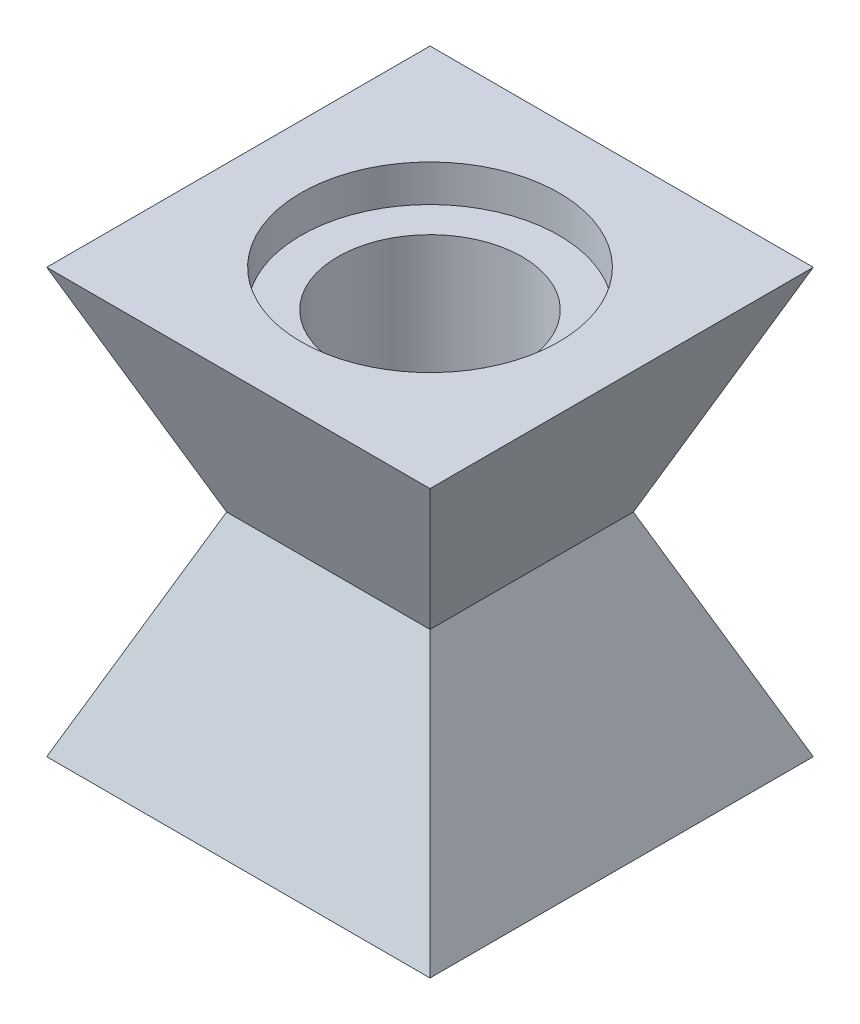
SolidWorks part; units mm, degrees
material "Cast Stainless Steel"
ref_plane "Front Plane" through (0, 0, 0) normal (0, 0, 1) x (1, 0, 0)
ref_plane "Top Plane" through (0, 0, 0) normal (0, 1, 0) x (1, 0, 0)
ref_plane "Right Plane" through (0, 0, 0) normal (1, 0, 0) x (0, 0, -1)
sketch "Sketch1" plane through (0, 0, 0) normal (0, 1, 0) x (1, 0, 0)
  line L1 (-52, 52) -> (52, 52)
  line L2 (-52, 52) -> (-52, -52)
  line L3 (-52, -52) -> (52, -52)
  line L4 (52, 52) -> (52, -52)
  line L5 (-52, 52) -> (52, -52) construction
  line L6 (-52, -52) -> (52, 52) construction
  circle A0 centre (0, 0) radius 25
  point P0 (0, 0)
  dimension "D2" = 50
  dimension "D1" = 104
  dimension "D3" = 104
extrude "Boss-Extrude1" add sketch "Sketch1" against normal blind 57.5 draft 23 contours L2 L1 L4 L3
ref_plane "Plane1" through (0, -57.5, 0) normal (0, 1, 0) x (1, 0, 0)
extrude "Cut-Extrude1" cut sketch "Sketch1<3>" against normal through all contours A0 region at (0, 0, 0)
sketch "Sketch1<3>" plane through (0, 0, 0) normal (0, 1, 0) x (1, 0, 0) same geometry as "Sketch1"
sketch "Sketch3" plane through (0, 0, 0) normal (0, 1, 0) x (1, 0, 0)
  circle A0 centre (0, 0) radius 35
  dimension "D1" = 70
extrude "Cut-Extrude2" cut sketch "Sketch3" against normal blind 10
mirror "Mirror2" about plane through (0, -57.5, 0) normal (0, 1, 0) of "Cut-Extrude2", "Cut-Extrude1", "Boss-Extrude1"
